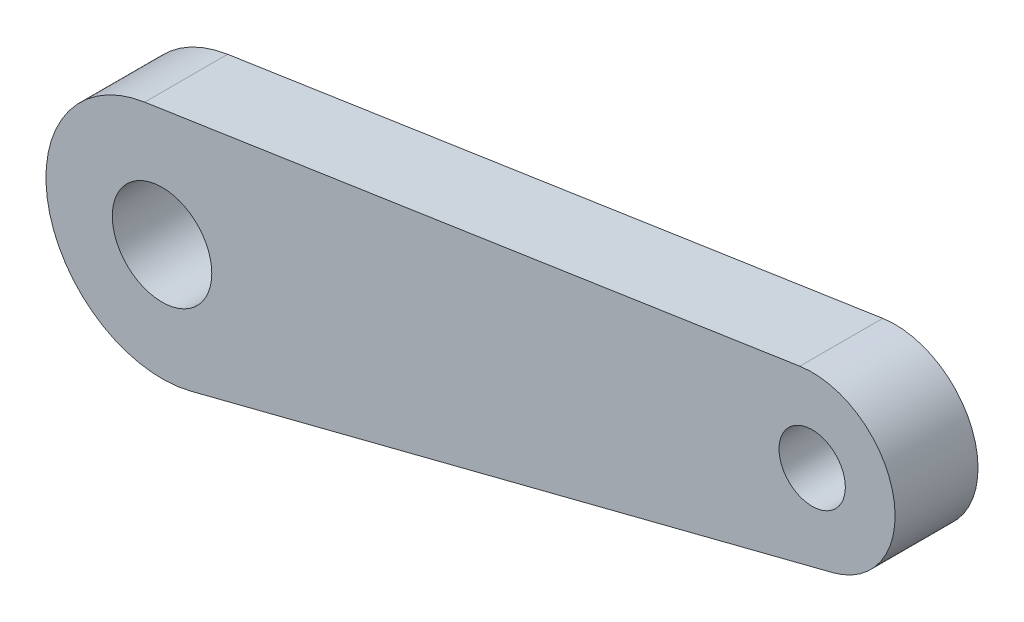
SolidWorks part; units mm, degrees
ref_plane "Front Plane" through (0, 0, 0) normal (0, 0, 1) x (1, 0, 0)
ref_plane "Top Plane" through (0, 0, 0) normal (0, 1, 0) x (1, 0, 0)
ref_plane "Right Plane" through (0, 0, 0) normal (1, 0, 0) x (0, 0, -1)
sketch "Sketch1" plane through (0, 0, 0) normal (0, 0, 1) x (1, 0, 0)
  line L0 (-61.0445, 24.9216) -> (-21.5418, 30.8829)
  line L1 (-19.5596, 21.0941) -> (-58.2694, 11.2173)
  circle A0 centre (-60, 18) radius 3 construction
  circle A1 centre (-20.7957, 25.9389) radius 2 construction
  circle A2 centre (-60, 18) radius 3
  circle A3 centre (-20.7957, 25.9389) radius 2
  arc A4 (-21.5418, 30.8829) -> (-19.5596, 21.0941) centre (-20.7957, 25.9389) cw
  arc A5 (-58.2694, 11.2173) -> (-61.0445, 24.9216) centre (-60, 18) cw
  dimension "D1" = 5
  dimension "D2" = 7
extrude "Boss-Extrude1" add sketch "Sketch1" along normal blind 5 from offset 10
